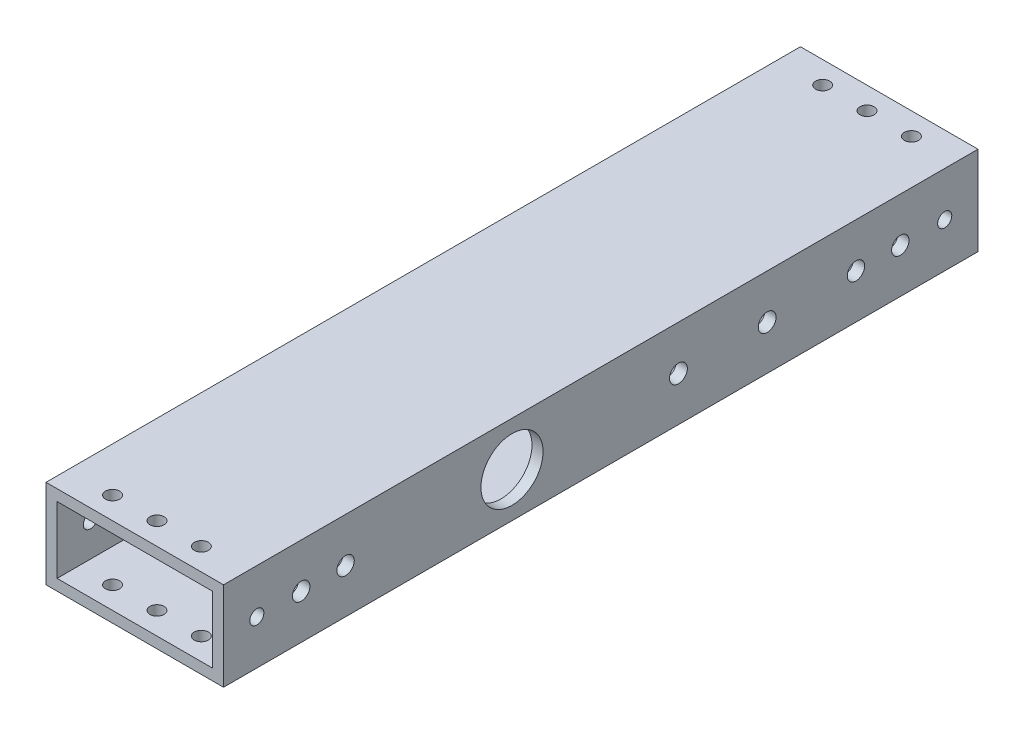
SolidWorks part; units mm, degrees
material "6061-T6 (SS)"
ref_plane "Front Plane" through (0, 0, 0) normal (0, 0, 1) x (1, 0, 0)
ref_plane "Top Plane" through (0, 0, 0) normal (0, 1, 0) x (1, 0, 0)
ref_plane "Right Plane" through (0, 0, 0) normal (1, 0, 0) x (0, 0, -1)
sketch "Sketch1" plane through (0, 0, 0) normal (0, 0, 1) x (1, 0, 0)
  line L0 (-22.225, 9.525) -> (22.225, 9.525)
  line L1 (-25.4, -12.7) -> (25.4, -12.7)
  line L2 (-25.4, -12.7) -> (-25.4, 12.7)
  line L3 (-25.4, 12.7) -> (25.4, 12.7)
  line L4 (25.4, -12.7) -> (25.4, 12.7)
  line L5 (-25.4, -12.7) -> (25.4, 12.7) construction
  line L6 (-25.4, 12.7) -> (25.4, -12.7) construction
  line L7 (22.225, -9.525) -> (22.225, 9.525)
  line L8 (-22.225, -9.525) -> (22.225, -9.525)
  line L9 (-22.225, -9.525) -> (-22.225, 9.525)
  point P0 (0, 0)
  dimension "D1" = 50.8
  dimension "D2" = 25.4
  dimension "D3" = 3.175
extrude "Boss-Extrude1" add sketch "Sketch1" along normal mid plane 215.9
sketch "Sketch2" plane through (25.4, 0, 0) normal (1, 0, 0) x (0, 0, -1)
  line L0 (-107.95, -12.7) -> (-107.95, 12.7) construction
  line L1 (0, 12.7) -> (0, -12.7) construction
  line L2 (-107.95, 12.7) -> (107.95, 12.7) construction
  line L3 (-107.95, -12.7) -> (107.95, -12.7) construction
  circle A0 centre (-98.425, 0) radius 2.0193
  circle A1 centre (98.425, 0) radius 2.0193
  circle A2 centre (-85.725, 0) radius 2.4892
  circle A3 centre (-73.025, 0) radius 2.4892
  circle A4 centre (73.025, 0) radius 2.4892
  circle A5 centre (85.725, 0) radius 2.4892
  dimension "D2" = 4.0386
  dimension "D5" = 4.9784
  dimension "D1" = 9.525
  dimension "D3" = 12.7
  dimension "D4" = 12.7
extrude "Cut-Extrude1" cut sketch "Sketch2" against normal through all
sketch "Sketch3" plane through (0, 12.7, 0) normal (0, 1, 0) x (1, 0, 0)
  line L0 (-25.4, 0) -> (25.4, 0) construction
  line L1 (-25.4, -107.95) -> (-25.4, 107.95) construction
  line L2 (25.4, -107.95) -> (25.4, 107.95) construction
  line L3 (25.4, -107.95) -> (-25.4, -107.95) construction
  circle A0 centre (-12.7, -101.6) radius 2.0193
  circle A1 centre (0, -101.6) radius 2.0193
  circle A2 centre (12.7, -101.6) radius 2.0193
  circle A3 centre (12.7, 101.6) radius 2.0193
  circle A4 centre (0, 101.6) radius 2.0193
  circle A5 centre (-12.7, 101.6) radius 2.0193
  dimension "D1" = 4.0386
  dimension "D2" = 12.7
  dimension "D3" = 12.7
  dimension "D4" = 6.35
extrude "Cut-Extrude2" cut sketch "Sketch3" against normal through all
sketch "Sketch4" plane through (25.4, 0, 0) normal (1, 0, 0) x (0, 0, -1)
  line L0 (-25.4, 0) -> (-45.1908, 0) construction
  line L1 (-16.51, 0) -> (-34.29, 0) construction
  line L8 (-25.4, 0) -> (47.625, 0) construction
  line L9 (0, 12.7) -> (0, -12.7) construction
  line L10 (-107.95, 12.7) -> (107.95, 12.7) construction
  line L11 (-107.95, -12.7) -> (107.95, -12.7) construction
  circle A0 centre (-25.4, 0) radius 8.89
  circle A9 centre (47.625, 0) radius 2.5527
  circle A10 centre (22.225, 0) radius 2.5527
  point P7 (-45.1908, 0)
  point P8 (22.225, 0)
  dimension "D2" = 17.78
  dimension "D3" = 25.4
  dimension "D1" = 73.025
  dimension "D4" = 5.1054
  dimension "D6" = 47.625
extrude "Cut-Extrude3" cut sketch "Sketch4" against normal through all contours A0 | A9 | A10
sketch "Sketch5" plane through (0, -12.7, 0) normal (0, -1, 0) x (1, 0, 0)
  line L0 (-25.4, 107.95) -> (-25.4, -107.95) construction
  line L1 (-25.4, 107.95) -> (25.4, 107.95) construction
  line L2 (-16.51, -12.7) -> (-3.81, -12.7) construction
  line L3 (-16.51, -12.7) -> (-16.51, 0) construction
  circle A0 centre (-3.81, 63.5) radius 2.5527
  circle A1 centre (-16.51, 63.5) radius 2.5527
  circle A2 centre (-16.51, 50.8) radius 2.5527
  circle A3 centre (-3.81, 50.8) radius 2.5527
  circle A4 centre (-16.51, -12.7) radius 2.5527
  circle A5 centre (-3.81, -12.7) radius 2.5527
  circle A6 centre (-3.81, 0) radius 2.5527
  circle A7 centre (-16.51, 0) radius 2.5527
  dimension "D3" = 5.1054
  dimension "D4" = 8.89
  dimension "D7" = 12.7
  dimension "D12" = 50.8
  dimension "D5" = 44.45
  dimension "D6" = 12.7
  dimension "D10" = 12.7
  dimension "D11" = 12.7
  dimension "D1" = 2
  dimension "D2" = 2
  dimension "D8" = 2
  dimension "D9" = 2
extrude "Cut-Extrude4" cut sketch "Sketch5" against normal up to next
